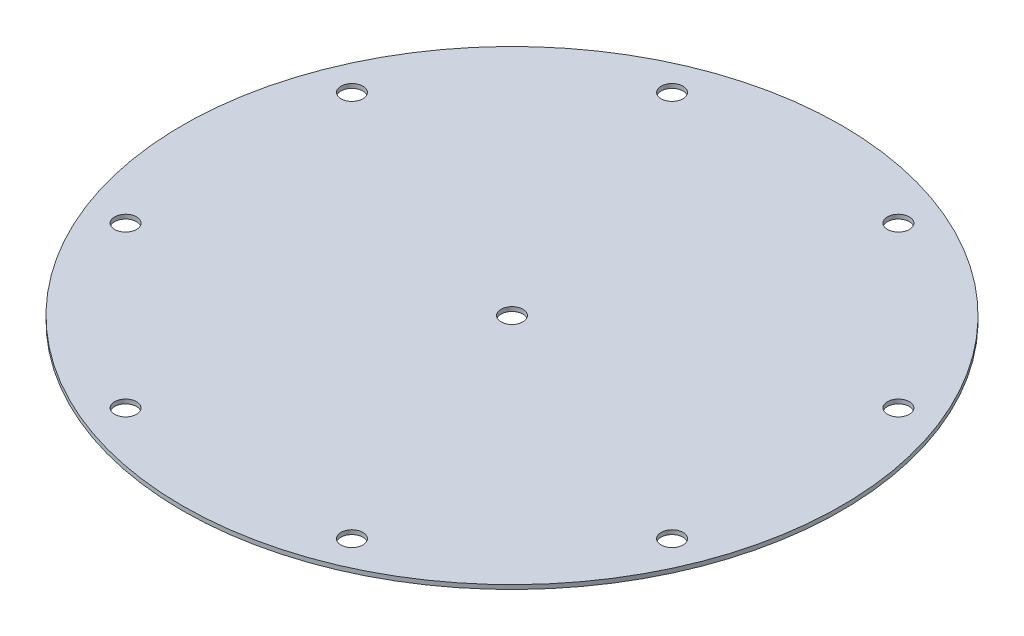
SolidWorks part; units mm, degrees
ref_plane "Front Plane" through (0, 0, 0) normal (0, 0, 1) x (1, 0, 0)
ref_plane "Top Plane" through (0, 0, 0) normal (0, 1, 0) x (1, 0, 0)
ref_plane "Right Plane" through (0, 0, 0) normal (1, 0, 0) x (0, 0, -1)
sketch "Sketch2" plane through (0, 0, 0) normal (1, 0, 0) x (0, 0, -1)
  line L0 (0, 0) -> (-77.9998, 0)
  line L1 (-77.9998, 0) -> (-77.9998, 1)
  line L2 (-77.9998, 1) -> (0, 1)
  line L5 (0, 1) -> (0, 0)
  dimension "D1" = 77.9998
  dimension "D2" = 1
ref_axis "Axis1" through (0, -0.75, 0) along (0, 1, 0)
revolve "Revolve1" add sketch "Sketch2" angle 360 about axis through (0, -0.75, 0) along (0, 1, 0)
hole_wizard "#6 (0.204) Diameter Hole1" positions "Sketch6" profile "Sketch7" hole size "#6" standard "ANSI Inch" end condition through all
sketch "Sketch6" plane through (0, 1, 0) normal (0, 1, 0) x (1, 0, 0)
  line L0 (0, 0) -> (-53.438, 129.0108) construction
  line L2 (0, 0) -> (0, 109.0908) construction
  point P0 (-26.7878, 64.6716)
  dimension "D1" = 22.5
  dimension "D2" = 70
sketch "Sketch7" plane through (-26.7878, 1, -64.6716) normal (1, 0, 0) x (0, 0, 1)
  line L0 (0, 0) -> (0, 1)
  line L1 (0, 1) -> (2.5908, 1)
  line L2 (2.5908, 1) -> (2.5908, 0)
  line L5 (2.5908, 0) -> (0, 0)
  line L11 (0, -6.35) -> (0, 107.95) construction
  dimension "Thru Hole Dia." = 5.1816
  dimension "Thru Hole Depth" = 1
pattern_circular "CirPattern3" count 8 over 360 about axis through (0, -0.75, 0) along (0, 1, 0) of "#6 (0.204) Diameter Hole1"
hole_wizard "#6 (0.204) Diameter Hole2" positions "Sketch8" profile "Sketch9" hole size "#6" standard "ANSI Inch" end condition through all
sketch "Sketch8" plane through (0, 1, 0) normal (0, 1, 0) x (1, 0, 0)
  line L0 (0, 0) -> (106.3094, -1.7118) construction
  point P7 (0, 0)
sketch "Sketch9" plane through (0, 1, 0) normal (1, 0, 0) x (0, 0, 1)
  line L0 (0, 0) -> (0, 1)
  line L1 (0, 1) -> (2.5908, 1)
  line L2 (2.5908, 1) -> (2.5908, 0)
  line L5 (2.5908, 0) -> (0, 0)
  line L11 (0, -6.35) -> (0, 107.95) construction
  dimension "Thru Hole Dia." = 5.1816
  dimension "Thru Hole Depth" = 1
